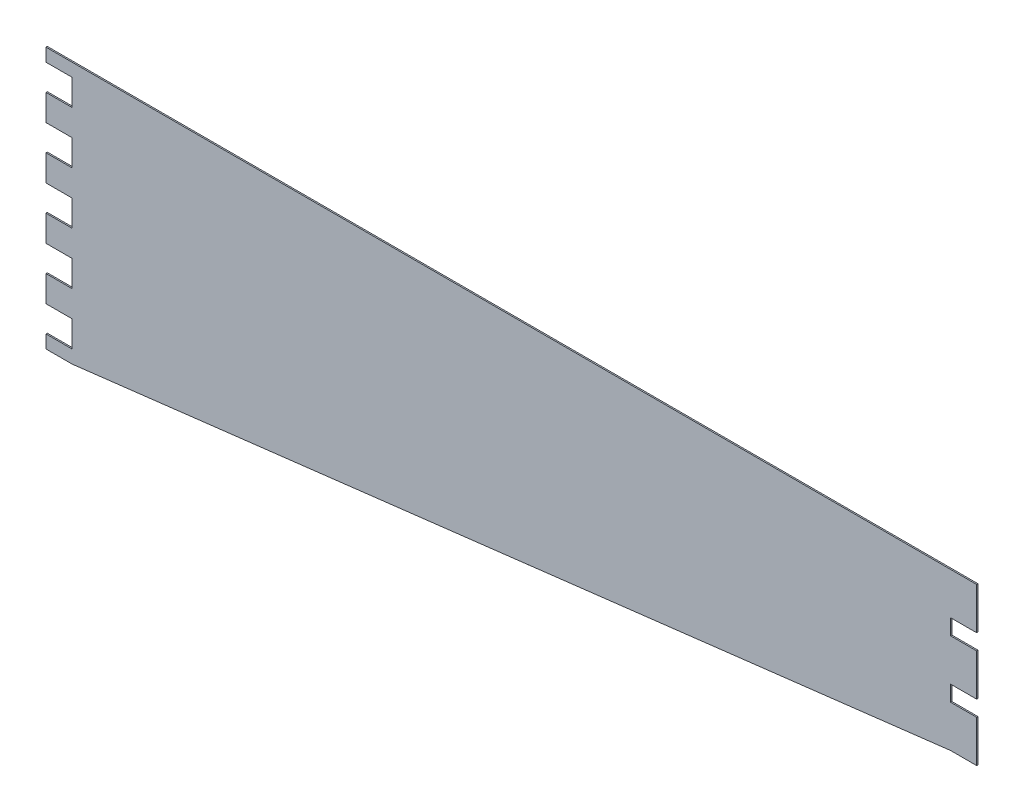
SolidWorks part; units mm, degrees
ref_plane "Front Plane" through (0, 0, 0) normal (0, 0, 1) x (1, 0, 0)
ref_plane "Top Plane" through (0, 0, 0) normal (0, 1, 0) x (1, 0, 0)
ref_plane "Right Plane" through (0, 0, 0) normal (1, 0, 0) x (0, 0, -1)
sketch "Sketch2" plane through (0, 0, 0) normal (0, 0, 1) x (1, 0, 0)
  line L0 (0, 0) -> (5, 0)
  line L1 (5, 0) -> (173, 20)
  line L2 (173, 20) -> (178, 20)
  line L3 (178, 20) -> (178, 50)
  line L4 (178, 50) -> (0, 50)
  line L5 (0, 50) -> (0, 0)
  dimension "D1" = 50
  dimension "D2" = 5
  dimension "D3" = 5
  dimension "D4" = 168
  dimension "D5" = 30
extrude "Boss-Extrude1" add sketch "Sketch2" along normal mid plane 0.25
sketch "Sketch3" plane through (0, 0, 0.125) normal (0, 0, 1) x (1, 0, 0)
  line L1 (0, 47.5) -> (5, 47.5)
  line L2 (0, 47.5) -> (0, 42.5)
  line L3 (0, 42.5) -> (5, 42.5)
  line L4 (5, 47.5) -> (5, 42.5)
  line L5 (178, 50) -> (0, 50) construction
  dimension "D1" = 5
  dimension "D2" = 5
  dimension "D3" = 2.5
extrude "Cut-Extrude1" cut sketch "Sketch3" against normal through all
pattern_linear "LPattern2" count 5 spacing 10 along (0, -1, 0) of "Cut-Extrude1"
sketch "Sketch4" plane through (0, 0, 0.125) normal (0, 0, 1) x (1, 0, 0)
  line L0 (178, 20) -> (178, 50) construction
  line L1 (178, 42) -> (173, 42)
  line L2 (178, 42) -> (178, 39)
  line L3 (178, 39) -> (173, 39)
  line L4 (173, 42) -> (173, 39)
  line L5 (178, 50) -> (0, 50) construction
  dimension "D1" = 5
  dimension "D2" = 3
  dimension "D3" = 8
extrude "Cut-Extrude2" cut sketch "Sketch4" against normal through all
pattern_linear "LPattern3" count 2 spacing 11 along (0, -1, 0) of "Cut-Extrude2"
